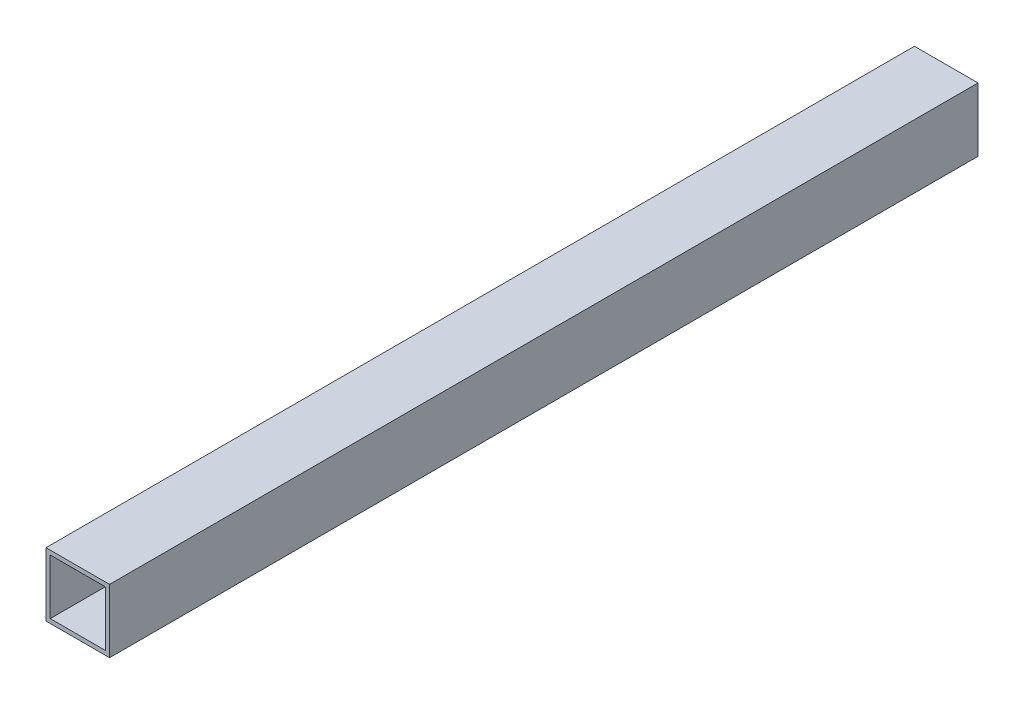
SolidWorks part; units mm, degrees
material "1060 合金"
ref_plane "前视基准面" through (0, 0, 0) normal (0, 0, 1) x (1, 0, 0)
ref_plane "上视基准面" through (0, 0, 0) normal (0, 1, 0) x (1, 0, 0)
ref_plane "右视基准面" through (0, 0, 0) normal (1, 0, 0) x (0, 0, -1)
other "Configuration Table"
sketch "草图1" plane through (0, 0, 0) normal (0, 0, 1) x (1, 0, 0)
  line L1 (0, 0) -> (15, 0)
  line L2 (0, 0) -> (0, -15)
  line L3 (0, -15) -> (15, -15)
  line L4 (15, 0) -> (15, -15)
  dimension "D1" = 15
  dimension "D2" = 15
extrude "拉伸-薄壁1" add sketch "草图1" along normal blind 205 thin thin type one direction reverse wall 1
sketch "草图2" plane through (0, -15, 0) normal (0, -1, 0) x (1, 0, 0)
  circle A1 centre (7.5, 825) radius 2.6
  circle A2 centre (7.5, 825) radius 2.6
  dimension "D1" = 0
extrude "切除-拉伸1" [suppressed] cut sketch "草图2" against normal up to next
